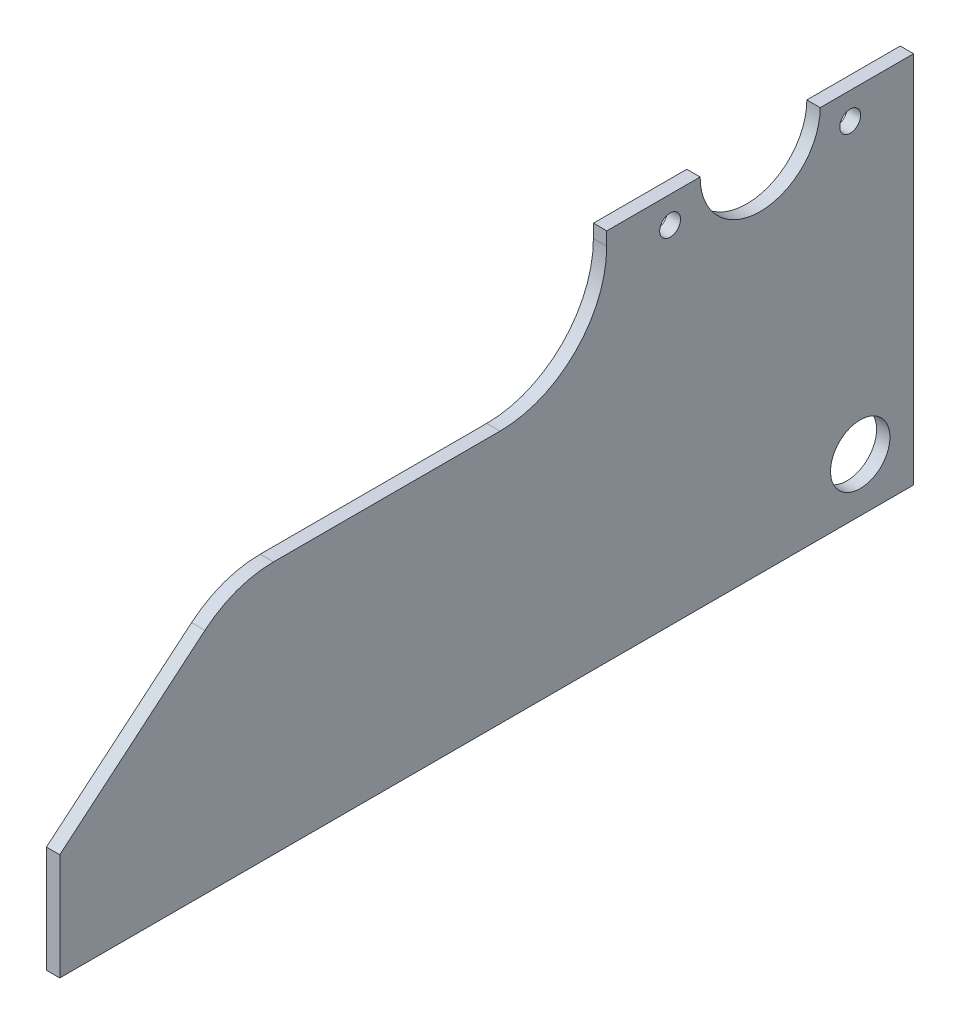
SolidWorks part; units mm, degrees
material "6061 Alloy"
ref_plane "Front Plane" through (0, 0, 0) normal (0, 0, 1) x (1, 0, 0)
ref_plane "Top Plane" through (0, 0, 0) normal (0, 1, 0) x (1, 0, 0)
ref_plane "Right Plane" through (0, 0, 0) normal (1, 0, 0) x (0, 0, -1)
sketch "Sketch1" plane through (0, 0, 0) normal (1, 0, 0) x (0, 0, -1)
  line L0 (0, -44.45) -> (0, 44.45)
  line L7 (0, 44.45) -> (-22.225, 44.45)
  line L8 (-50.8, 44.45) -> (-73.025, 44.45)
  line L10 (-98.425, 15.875) -> (-152.3332, 15.875)
  line L13 (-203.2, -44.45) -> (0, -44.45)
  line L14 (-203.2, -44.45) -> (-203.2, -19.05)
  line L15 (-203.2, -19.05) -> (-168.66, 9.9325)
  line L16 (-203.2, -19.05) -> (0, -19.05) construction
  line L18 (-73.025, 44.45) -> (-73.025, 41.275)
  arc A2 (-22.225, 44.45) -> (-50.8, 44.45) centre (-36.5125, 44.45) cw
  arc A4 (-152.3332, 15.875) -> (-168.66, 9.9325) centre (-152.3332, -9.525) ccw
  arc A6 (-73.025, 41.275) -> (-98.425, 15.875) centre (-98.425, 41.275) cw
  point P4 (0, 0)
  dimension "D1" = 28.575
  dimension "D4" = 25.4
  dimension "D7" = 25.4
  dimension "D2" = 88.9
  dimension "D3" = 73.025
  dimension "D5" = 3.175
  dimension "D6" = 203.2
  dimension "D8" = 50
extrude "Boss-Extrude1" add sketch "Sketch1" along normal blind 3.175
hole_wizard "#10 Clearance Hole1" positions "Sketch2" profile "Sketch3" hole size "#10" standard "ANSI Inch" end condition through all
sketch "Sketch2" plane through (3.175, 0, 0) normal (1, 0, 0) x (0, 0, -1)
  line L0 (-50.8, 44.45) -> (-73.025, 44.45) construction
  line L1 (-57.9437, 38.1) -> (-15.0812, 38.1) construction
  line L3 (-36.5125, 38.1) -> (-36.5125, 44.45) construction
  point P0 (-57.9437, 38.1)
  point P2 (-15.0812, 38.1)
  dimension "D1" = 42.8625
  dimension "D2" = 6.35
sketch "Sketch3" plane through (3.175, 38.1, 57.9437) normal (0, 1, 0) x (0, 0, -1)
  line L0 (0, 0) -> (0, 3.175)
  line L1 (0, 3.175) -> (2.4892, 3.175)
  line L2 (2.4892, 3.175) -> (2.4892, 0)
  line L5 (2.4892, 0) -> (0, 0)
  line L11 (0, -6.35) -> (0, 107.95) construction
  dimension "Thru Hole Dia." = 4.9784
  dimension "Thru Hole Depth" = 3.175
sketch "Sketch9" plane through (3.175, 0, 0) normal (1, 0, 0) x (0, 0, -1)
  line L2 (0, -44.45) -> (0, 44.45) construction
  line L3 (-203.2, -44.45) -> (0, -44.45) construction
  circle A0 centre (-12.7, -31.75) radius 7.0739
  dimension "D1" = 14.1478
  dimension "D3" = 12.7
  dimension "D2" = 12.7
extrude "Cut-Extrude1" cut sketch "Sketch9" against normal through all
